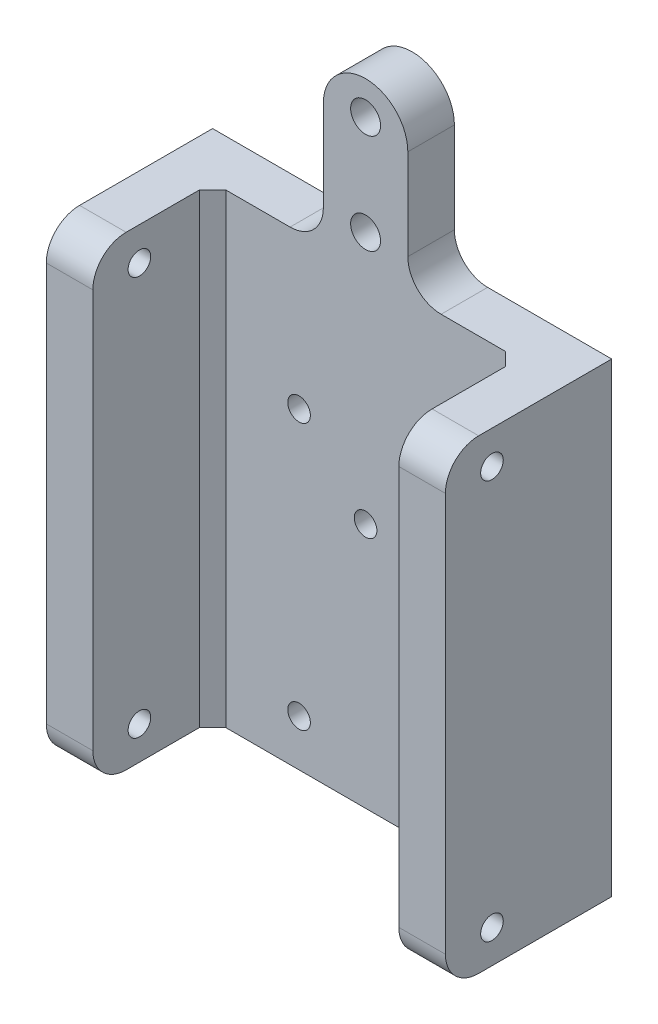
SolidWorks part; units mm, degrees
ref_plane "Front Plane" through (0, 0, 0) normal (0, 0, 1) x (1, 0, 0)
ref_plane "Top Plane" through (0, 0, 0) normal (0, 1, 0) x (1, 0, 0)
ref_plane "Right Plane" through (0, 0, 0) normal (1, 0, 0) x (0, 0, -1)
sketch "Sketch1" plane through (0, 0, 0) normal (0, 1, 0) x (1, 0, 0)
  line L1 (6.35, 3.5) -> (-6.35, 3.5)
  line L2 (6.35, 3.5) -> (6.35, -3.5)
  line L3 (6.35, -3.5) -> (-6.35, -3.5)
  line L4 (-6.35, 3.5) -> (-6.35, -3.5)
  line L5 (6.35, 3.5) -> (-6.35, -3.5) construction
  line L6 (6.35, -3.5) -> (-6.35, 3.5) construction
  point P0 (0, 0)
  dimension "D1" = 7
  dimension "D2" = 12.7
extrude "Boss-Extrude1" add sketch "Sketch1" along normal blind 25
hole_wizard "M4 Clearance Hole1" positions "Sketch2" profile "Sketch3" hole size "M4" standard "ANSI Metric" end condition through all
sketch "Sketch2" plane through (0, 0, 3.5) normal (0, 0, 1) x (1, 0, 0)
  line L0 (-6.35, 0) -> (6.35, 0) construction
  point P0 (0, 5)
  point P2 (0, 20)
  point P7 (0, 0)
  point P8 (0, 0)
  dimension "D1" = 15
  dimension "D2" = 5
sketch "Sketch3" plane through (0, 5, 3.5) normal (1, 0, 0) x (0, -1, 0)
  line L0 (0, 0) -> (0, 7)
  line L1 (0, 7) -> (2.25, 7)
  line L2 (2.25, 7) -> (2.25, 0)
  line L5 (2.25, 0) -> (0, 0)
  line L11 (0, -6.35) -> (0, 107.95) construction
  dimension "Thru Hole Dia." = 4.5
  dimension "Thru Hole Depth" = 7
sketch "Sketch4" plane through (0, 0, 0) normal (0, 1, 0) x (1, 0, 0)
  line L0 (-6.35, -3.5) -> (6.35, -3.5) construction
  line L1 (-23, 3.5) -> (23, 3.5)
  line L2 (-23, 3.5) -> (-23, -3.5)
  line L3 (-23, -3.5) -> (23, -3.5)
  line L4 (23, 3.5) -> (23, -3.5)
  line L5 (0, -3.5) -> (0, 3.5) construction
  line L6 (-23, 0) -> (23, 0) construction
  line L7 (6.35, 3.5) -> (-6.35, 3.5) construction
  point P4 (0, -2.5)
  point P412 (0, 0)
  dimension "D2" = 46
extrude "Boss-Extrude2" add sketch "Sketch4" against normal blind 70
sketch "Sketch5" plane through (0, 0, 0) normal (0, 1, 0) x (1, 0, 0)
  line L0 (0, 0) -> (0, -3.5) construction
  line L1 (-6.35, -3.5) -> (6.35, -3.5) construction
  line L2 (-23, -9) -> (-30, -9) construction
  line L3 (23, 3.5) -> (30, 3.5)
  line L4 (23, 3.5) -> (23, -21.5)
  line L5 (23, -21.5) -> (30, -21.5)
  line L6 (30, 3.5) -> (30, -21.5)
  line L7 (26.5, -21.5) -> (26.5, 3.5) construction
  line L8 (23, -9) -> (30, -9) construction
  line L9 (-26.5, -21.5) -> (-26.5, 3.5) construction
  line L10 (-30, 3.5) -> (-30, -21.5)
  line L11 (-23, -21.5) -> (-30, -21.5)
  line L12 (-23, 3.5) -> (-23, -21.5)
  line L13 (-23, 3.5) -> (-30, 3.5)
  point P17 (-26.5, -9)
  point P261 (26.5, -9)
  dimension "D1" = 25
  dimension "D2" = 7
extrude "Boss-Extrude3" add sketch "Sketch5" against normal blind 70
hole_wizard "M3 Clearance Hole1" positions "Sketch6" profile "Sketch7" hole size "M3" standard "ANSI Metric" end condition through all
sketch "Sketch6" plane through (30, 0, 0) normal (1, 0, 0) x (0, 0, -1)
  line L0 (-21.5, -35) -> (3.5, -35) construction
  line L1 (-21.5, -70) -> (-21.5, 0) construction
  line L2 (3.5, -70) -> (3.5, 0) construction
  line L4 (-3.5, 25) -> (-3.5, 0) construction
  point P0 (-14.5, -5)
  point P2 (-14.5, -65)
  dimension "D1" = 60
  dimension "D2" = 11
sketch "Sketch7" plane through (30, -5, 14.5) normal (0, 1, 0) x (0, 0, -1)
  line L0 (0, 0) -> (0, 60)
  line L1 (0, 60) -> (1.7, 60)
  line L2 (1.7, 60) -> (1.7, 0)
  line L5 (1.7, 0) -> (0, 0)
  line L11 (0, -6.35) -> (0, 107.95) construction
  dimension "Thru Hole Dia." = 3.4
  dimension "Thru Hole Depth" = 60
hole_wizard "M3 Clearance Hole2" positions "Sketch8" profile "Sketch9" hole size "M3" standard "ANSI Metric" end condition through all
sketch "Sketch8" plane through (0, 0, -3.5) normal (0, 0, -1) x (-1, 0, 0)
  point P0 (-10, -23)
  point P2 (10, -23)
  point P5 (0, -33)
  point P8 (-10, -63)
  point P11 (10, -63)
  point P15 (-10, -23)
sketch "Sketch9" plane through (10, -23, -3.5) normal (1, 0, 0) x (0, 1, 0)
  line L0 (0, 0) -> (0, 25)
  line L1 (0, 25) -> (1.7, 25)
  line L2 (1.7, 25) -> (1.7, 0)
  line L5 (1.7, 0) -> (0, 0)
  line L11 (0, -6.35) -> (0, 107.95) construction
  dimension "Thru Hole Dia." = 3.4
  dimension "Thru Hole Depth" = 25
fillet "Fillet1" 2 edges at (-6.35, 25, 0) (6.35, 25, 0) type full round first side face at (-6.35, 12.5, 0) second side face at (6.35, 12.5, 0) middle face at (0, 25, 0)
fillet "Fillet2" radius 5 6 edges at (26.5, -70, 21.5) (-26.5, -70, 21.5) (-26.5, 0, 21.5) (26.5, 0, 21.5) (-6.35, 0, 0) (6.35, 0, 0)
fillet "Fillet3" [suppressed] radius 7 profile chamfer
fillet "Fillet4" radius 2 2 edges at (23, -35, 3.5) (-23, -35, 3.5) profile chamfer
